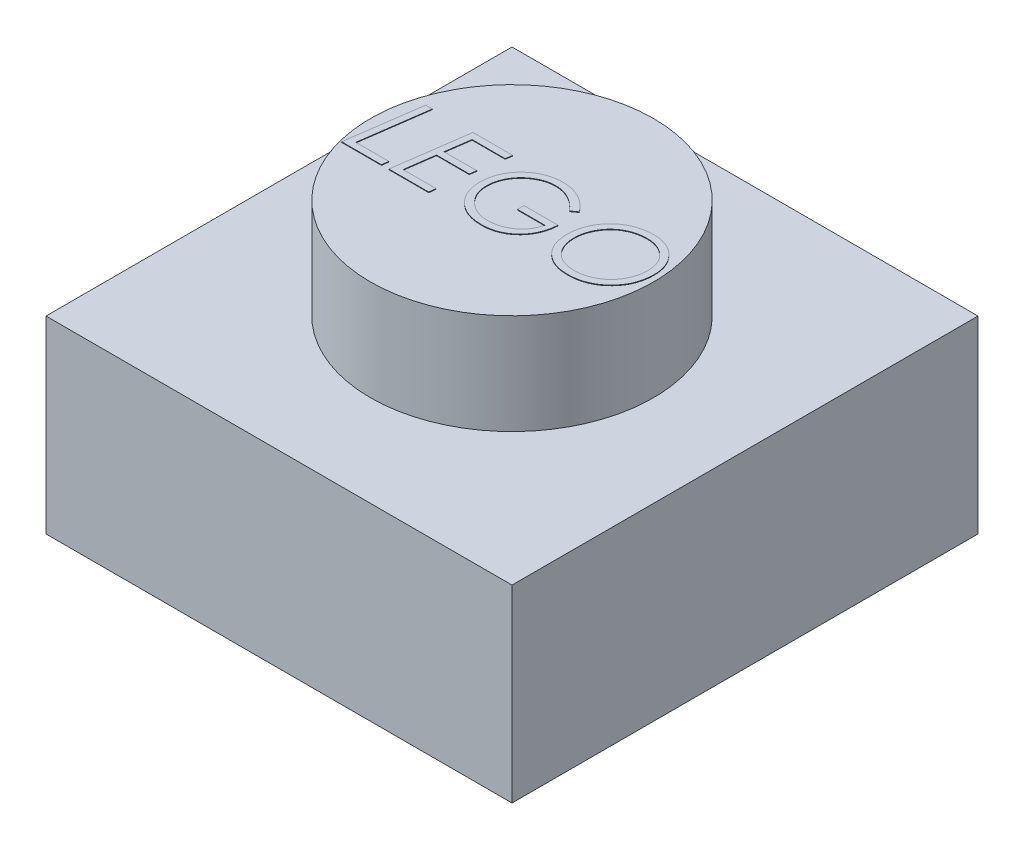
SolidWorks part; units mm, degrees
ref_plane "Front Plane" through (0, 0, 0) normal (0, 0, 1) x (1, 0, 0)
ref_plane "Top Plane" through (0, 0, 0) normal (0, 1, 0) x (1, 0, 0)
ref_plane "Right Plane" through (0, 0, 0) normal (1, 0, 0) x (0, 0, -1)
sketch "Sketch1" plane through (0, 0, 0) normal (0, 1, 0) x (1, 0, 0)
  line L0 (0, 0) -> (7.9, 0)
  line L1 (7.9, 0) -> (7.9, 7.9)
  line L2 (0, 0) -> (0, 7.9)
  line L3 (0, 7.9) -> (7.9, 7.9)
  dimension "D1" = 7.9
  dimension "D2" = 7.9
  dimension "D3" = 7.9
extrude "Boss-Extrude1" add sketch "Sketch1" along normal blind 3.2
sketch "Sketch2" plane through (0, 3.2, 0) normal (0, 1, 0) x (1, 0, 0)
  line L0 (0, 7.9) -> (7.9, 0) construction
  circle A0 centre (3.95, 3.95) radius 2.4
extrude "Boss-Extrude2" add sketch "Sketch2" along normal blind 1.7
sketch "Sketch3" plane through (0, 4.9, 0) normal (0, 1, 0) x (1, 0, 0)
  line L0 (1.625, 3.3549) -> (6.275, 3.3549) construction
  circle A0 centre (3.95, 3.95) radius 2.4 construction
  circle A1 centre (3.95, 3.95) radius 2.4 construction
  text T0 "<i>LEGO</i>" font "Century Gothic" height 1.25
extrude "Boss-Extrude4" add sketch "Sketch3" along normal blind 0.01
sketch "Sketch4" plane through (0, 0, 0) normal (0, -1, 0) x (1, 0, 0)
  line L0 (7.9, -7.9) -> (0, -7.9) construction
  line L1 (7.3, -7.3) -> (0.6204, -7.3)
  line L2 (7.3, -7.3) -> (7.3, -0.6204)
  line L3 (7.3, -0.6204) -> (0.6204, -0.6204)
  line L4 (0.6204, -7.3) -> (0.6204, -0.6204)
  line L5 (7.9, 0) -> (7.9, -7.9) construction
  dimension "D1" = 0.6
  dimension "D2" = 0.6
extrude "Cut-Extrude1" cut sketch "Sketch4" against normal blind 2.01 contours L2 L1 L4 L3
sketch "Sketch5" plane through (0, 3.2, 0) normal (0, 1, 0) x (1, 0, 0)
  line L1 (1.4581, 1.5578) -> (6.3695, 1.5578)
  line L2 (1.4581, 1.5578) -> (1.4581, 6.3652)
  line L3 (1.4581, 6.3652) -> (6.3695, 6.3652)
  line L4 (6.3695, 1.5578) -> (6.3695, 6.3652)
  circle A1 centre (6.3695, 6.3652) radius 1.0161
  circle A2 centre (6.3695, 1.5578) radius 1.0061
  circle A3 centre (1.4581, 1.5578) radius 1.0219
  circle A4 centre (1.4581, 6.3652) radius 1.0411
  circle M5 centre (3.95, 3.95) radius 2.4
extrude "Boss-Extrude5" add sketch "Sketch5" against normal blind 2.01 contours L1 A2 L4 | L2 A3 L1 | L1 A3 L2 | L4 A2 L1 M5 | L4 A1 L3 | L3 A1 L4 | L2 A4 L3 | L3 A4 L2 region at (1.8919, 3.2, -1.9915) region at (1.3136, 3.2, -1.4132) region at (1.3108, 3.2, -6.5125) region at (1.9, 3.2, -5.9234) region at (5.9427, 3.2, -1.9847) region at (6.5119, 3.2, -1.4155) region at (6.5133, 3.2, -6.509) region at (5.9383, 3.2, -5.934)
